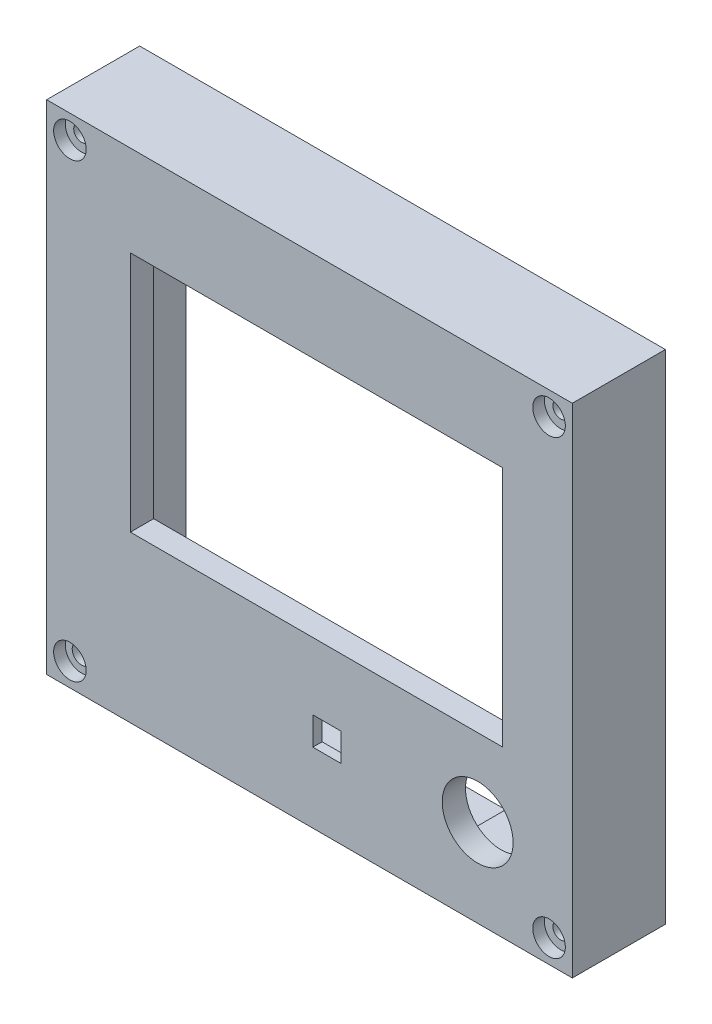
SolidWorks part; units mm, degrees
ref_plane "Front Plane" through (0, 0, 0) normal (0, 0, 1) x (1, 0, 0)
ref_plane "Top Plane" through (0, 0, 0) normal (0, 1, 0) x (1, 0, 0)
ref_plane "Right Plane" through (0, 0, 0) normal (1, 0, 0) x (0, 0, -1)
sketch "Sketch1" plane through (0, 0, 0) normal (0, 0, 1) x (1, 0, 0)
  line L1 (-56.5, -53.5) -> (56.5, -53.5)
  line L2 (-56.5, -53.5) -> (-56.5, 53.5)
  line L3 (-56.5, 53.5) -> (56.5, 53.5)
  line L4 (56.5, -53.5) -> (56.5, 53.5)
  line L5 (-56.5, -53.5) -> (56.5, 53.5) construction
  line L6 (-56.5, 53.5) -> (56.5, -53.5) construction
  point P0 (0, 0)
  dimension "D1" = 113
  dimension "D2" = 107
extrude "Boss-Extrude1" add sketch "Sketch1" along normal blind 5
sketch "Sketch6" plane through (0, 0, 5) normal (0, 0, 1) x (1, 0, 0)
  line L0 (51.5, 48.5) -> (51.5, -48.5) construction
  line L1 (51.5, -48.5) -> (-51.5, -48.5) construction
  line L2 (-51.5, -48.5) -> (-51.5, 48.5) construction
  line L3 (-51.5, 48.5) -> (51.5, 48.5) construction
  line L4 (56.5, -53.5) -> (56.5, 53.5) construction
  line L5 (-56.5, 53.5) -> (-56.5, -53.5) construction
  line L6 (56.5, 53.5) -> (-56.5, 53.5) construction
  line L7 (-56.5, -53.5) -> (56.5, -53.5) construction
  circle A0 centre (-51.5, 48.5) radius 3.5
  circle A1 centre (-51.5, -48.5) radius 3.5
  circle A2 centre (51.5, -48.5) radius 3.5
  circle A3 centre (51.5, 48.5) radius 3.5
  dimension "D5" = 7
  dimension "D6" = 7
  dimension "D7" = 7
  dimension "D8" = 7
  dimension "D1" = 5
  dimension "D2" = 5
  dimension "D3" = 5
  dimension "D4" = 5
extrude "Cut-Extrude3" cut sketch "Sketch6" against normal blind 2.5
sketch "Sketch7" plane through (0, 0, 5) normal (0, 0, 1) x (1, 0, 0)
  line L0 (-56.5, 53.5) -> (-56.5, -53.5) construction
  line L1 (-38.5, 34) -> (41.5, 34)
  line L2 (-38.5, 34) -> (-38.5, -18)
  line L3 (-38.5, -18) -> (41.5, -18)
  line L4 (41.5, 34) -> (41.5, -18)
  line L5 (-38.5, 34) -> (41.5, -18) construction
  line L6 (-38.5, -18) -> (41.5, 34) construction
  line L7 (56.5, 53.5) -> (-56.5, 53.5) construction
  line L8 (56.5, -53.5) -> (56.5, 53.5) construction
  line L9 (-56.5, -53.5) -> (56.5, -53.5) construction
  line L11 (0.71, -38.42) -> (6.7298, -38.42)
  line L12 (0.71, -38.42) -> (0.71, -32.4002)
  line L13 (0.71, -32.4002) -> (6.7298, -32.4002)
  line L14 (6.7298, -38.42) -> (6.7298, -32.4002)
  line L15 (0.71, -38.42) -> (6.7298, -32.4002) construction
  line L16 (0.71, -32.4002) -> (6.7298, -38.42) construction
  circle A0 centre (36.1495, -34.6735) radius 7.62
  point P0 (1.5, 8)
  point P15 (3.7199, -35.4101)
  dimension "D5" = 15.24
  dimension "D1" = 52
  dimension "D2" = 80
  dimension "D3" = 18
  dimension "D4" = 19.5
  dimension "D6" = 20.3505
  dimension "D7" = 18.8265
  dimension "D8" = 6.0198
  dimension "D9" = 6.0198
  dimension "D10" = 15.08
  dimension "D11" = 57.21
extrude "Cut-Extrude4" cut sketch "Sketch7" against normal through all
sketch "Sketch9" plane through (0, 0, 0) normal (0, 0, -1) x (-1, 0, 0)
  line L0 (-6.7298, -32.4002) -> (-0.71, -32.4002) construction
  line L1 (-6.7298, -38.42) -> (-6.7298, -32.4002) construction
  line L2 (-0.71, -38.42) -> (-6.7298, -38.42) construction
  line L3 (-0.71, -32.4002) -> (-0.71, -38.42) construction
  line L4 (-6.7298, -32.4002) -> (-0.71, -32.4002) construction
  line L5 (-6.7298, -38.42) -> (-6.7298, -32.4002) construction
  line L6 (-0.71, -38.42) -> (-6.7298, -38.42) construction
  line L7 (-0.71, -32.4002) -> (-0.71, -38.42) construction
  line L8 (1.29, -40.42) -> (-8.7298, -40.42)
  line L9 (-8.7298, -40.42) -> (-8.7298, -30.4002)
  line L10 (-8.7298, -30.4002) -> (1.29, -30.4002)
  line L11 (1.29, -30.4002) -> (1.29, -40.42)
  dimension "D1" = 2
extrude "Cut-Extrude5" cut sketch "Sketch9" against normal blind 2
sketch "Sketch10" plane through (0, 0, 2.5) normal (0, 0, 1) x (1, 0, 0)
  circle A0 centre (-51.5, 48.5) radius 1.6801
  circle A1 centre (51.5, 48.5) radius 1.6801
  circle A2 centre (51.5, -48.5) radius 1.6801
  circle A3 centre (-51.5, -48.5) radius 2
  dimension "D1" = 4
extrude "Cut-Extrude6" cut sketch "Sketch10" against normal through all
sketch "Sketch11" plane through (0, 0, 0) normal (0, 0, -1) x (-1, 0, 0)
  line L1 (40.4022, -49.3262) -> (-28.0141, -49.3262)
  line L2 (40.4022, -49.3262) -> (40.4022, -18.9693)
  line L3 (40.4022, -18.9693) -> (-28.0141, -18.9693)
  line L4 (-28.0141, -49.3262) -> (-28.0141, -18.9693)
  line L5 (40.4022, -49.3262) -> (-28.0141, -18.9693) construction
  line L6 (40.4022, -18.9693) -> (-28.0141, -49.3262) construction
  point P0 (6.1941, -34.1478)
extrude "Cut-Extrude10" cut sketch "Sketch11" against normal blind 3
sketch "Sketch12" plane through (0, 0, 0) normal (0, 0, -1) x (-1, 0, 0)
  line L0 (56.5, -53.5) -> (-56.5, -53.5) construction
  line L1 (56.5, 53.5) -> (46.5, 53.5)
  line L2 (56.5, 53.5) -> (56.5, -53.5)
  line L3 (56.5, -53.5) -> (46.5, -53.5)
  line L4 (46.5, 43.5) -> (46.5, -43.5)
  line L5 (-56.5, -53.5) -> (-56.5, 53.5) construction
  line L6 (56.5, -53.5) -> (-56.5, -53.5)
  line L7 (56.5, -53.5) -> (56.5, -43.5)
  line L8 (46.5, -43.5) -> (-46.5, -43.5)
  line L9 (-56.5, -53.5) -> (-56.5, -43.5)
  line L11 (-56.5, 53.5) -> (-46.5, 53.5)
  line L12 (-56.5, 53.5) -> (-56.5, -53.5)
  line L13 (-56.5, -53.5) -> (-46.5, -53.5)
  line L14 (-46.5, 43.5) -> (-46.5, -43.5)
  line L15 (56.5, 53.5) -> (-56.5, 53.5)
  line L16 (56.5, 53.5) -> (56.5, 43.5)
  line L17 (46.5, 43.5) -> (-46.5, 43.5)
  line L18 (-56.5, 53.5) -> (-56.5, 43.5)
  line M9 (-28.0141, -49.3262) -> (-28.0141, -18.9693)
  line M11 (40.4022, -18.9693) -> (40.4022, -49.3262)
  line M12 (40.4022, -49.3262) -> (-28.0141, -49.3262)
  circle M13 centre (51.5, -48.5) radius 2
  circle M14 centre (-51.5, -48.5) radius 1.6801
  circle M15 centre (-51.5, 48.5) radius 1.6801
  circle M16 centre (51.5, 48.5) radius 1.6801
  line M22 (-56.5, 53.5) -> (-56.5, -53.5)
  line M23 (-56.5, -53.5) -> (56.5, -53.5)
  line M24 (56.5, -53.5) -> (56.5, 53.5)
  line M25 (56.5, 53.5) -> (-56.5, 53.5)
  dimension "D1" = 10
  dimension "D2" = 10
  dimension "D3" = 10
  dimension "D4" = 10
extrude "Boss-Extrude2" add sketch "Sketch12" along normal blind 15 contours L12 L6 L2 L17 L4 L8 L14 M25 M22 M23 M24 M11 M12 M9 M14 M16 M15 M13 region at (-54.9438, 48.5, 0)
